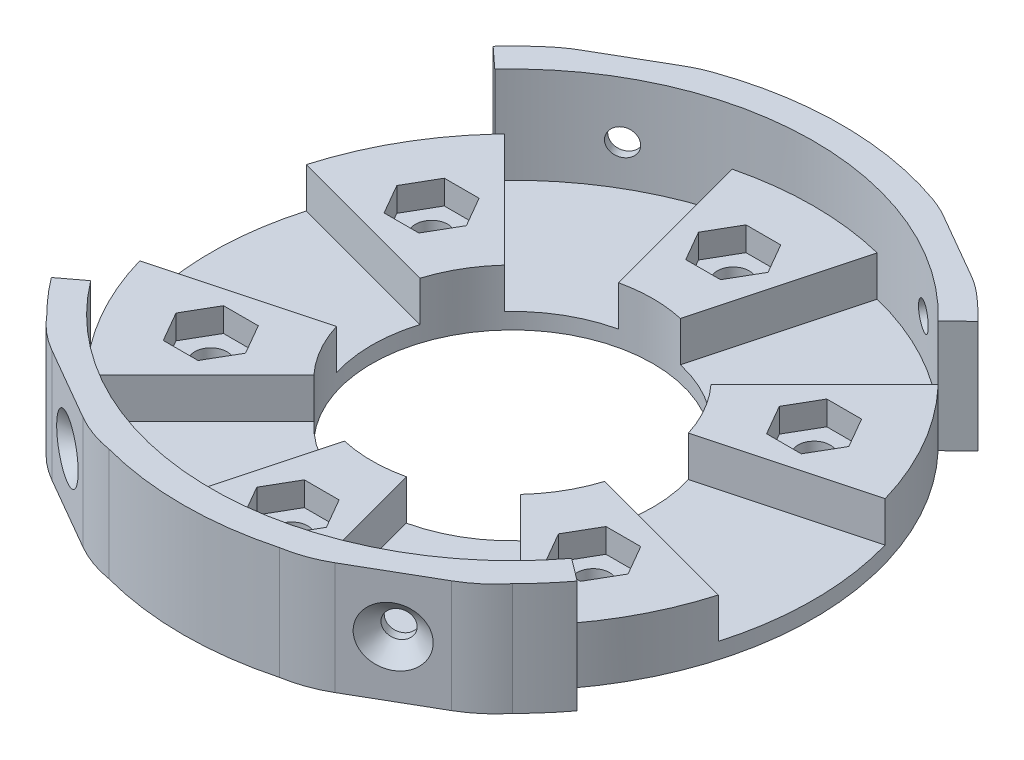
SolidWorks part; units mm, degrees
ref_plane "Front" through (0, 0, 0) normal (0, 0, 1) x (1, 0, 0)
ref_plane "Top" through (0, 0, 0) normal (0, 1, 0) x (1, 0, 0)
ref_plane "Right" through (0, 0, 0) normal (1, 0, 0) x (0, 0, -1)
sketch "Sketch1" plane through (0, 0, 0) normal (0, 1, 0) x (1, 0, 0)
  line L0 (21.6506, 17.5) -> (19.4856, 13.75)
  line L1 (4.3301, 27.5) -> (2.1651, 31.25)
  line L2 (2.1651, 31.25) -> (-2.1651, 31.25)
  line L3 (-2.1651, 31.25) -> (-4.3301, 27.5)
  line L4 (-4.3301, 27.5) -> (-2.1651, 23.75)
  line L5 (-2.1651, 23.75) -> (2.1651, 23.75)
  line L6 (2.1651, 23.75) -> (4.3301, 27.5)
  line L7 (25.9808, 17.5) -> (21.6506, 17.5)
  line L8 (28.1458, 13.75) -> (25.9808, 17.5)
  line L9 (25.9808, 10) -> (28.1458, 13.75)
  line L10 (19.4856, 13.75) -> (21.6506, 10)
  line L11 (21.6506, 10) -> (25.9808, 10)
  line L12 (25.9808, -10) -> (21.6506, -10)
  line L13 (28.1458, -13.75) -> (25.9808, -10)
  line L14 (25.9808, -17.5) -> (28.1458, -13.75)
  line L15 (21.6506, -17.5) -> (25.9808, -17.5)
  line L16 (21.6506, -10) -> (19.4856, -13.75)
  line L17 (19.4856, -13.75) -> (21.6506, -17.5)
  line L18 (4.3301, -27.5) -> (2.1651, -23.75)
  line L19 (2.1651, -31.25) -> (4.3301, -27.5)
  line L20 (-2.1651, -31.25) -> (2.1651, -31.25)
  line L21 (-4.3301, -27.5) -> (-2.1651, -31.25)
  line L22 (2.1651, -23.75) -> (-2.1651, -23.75)
  line L23 (-2.1651, -23.75) -> (-4.3301, -27.5)
  line L24 (-21.6506, -17.5) -> (-19.4856, -13.75)
  line L25 (-25.9808, -17.5) -> (-21.6506, -17.5)
  line L26 (-28.1458, -13.75) -> (-25.9808, -17.5)
  line L27 (-25.9808, -10) -> (-28.1458, -13.75)
  line L28 (-19.4856, -13.75) -> (-21.6506, -10)
  line L29 (-21.6506, -10) -> (-25.9808, -10)
  line L30 (-25.9808, 10) -> (-21.6506, 10)
  line L31 (-28.1458, 13.75) -> (-25.9808, 10)
  line L32 (-25.9808, 17.5) -> (-28.1458, 13.75)
  line L33 (-21.6506, 17.5) -> (-25.9808, 17.5)
  line L34 (-21.6506, 10) -> (-19.4856, 13.75)
  line L35 (-19.4856, 13.75) -> (-21.6506, 17.5)
  line L36 (23.8157, 13.75) -> (15.1554, 8.75)
  line L37 (23.8157, 13.75) -> (32.476, 18.75)
  line L38 (0, 0) -> (9.7057, 36.2222)
  line L39 (0, 0) -> (26.5165, 26.5165)
  line L40 (-9.0279, 36.3971) -> (-3.8496, 17.0713)
  line L41 (26.5165, 26.5165) -> (23.8157, 13.75)
  line L42 (0, 0) -> (36.2222, 9.7057)
  line L43 (0, 0) -> (36.2222, -9.7057)
  line L44 (0, 0) -> (26.5165, -26.5165)
  line L45 (0, 0) -> (9.7057, -36.2222)
  line L46 (0, 0) -> (-9.7057, -36.2222)
  line L47 (0, 0) -> (-26.5165, -26.5165)
  line L48 (0, 0) -> (-36.2222, -9.7057)
  line L49 (0, 0) -> (-36.2222, 9.7057)
  line L50 (0, 0) -> (-26.5165, 26.5165)
  line L51 (0, 0) -> (-9.7057, 36.2222)
  line L52 (0, 0) -> (0, 37.5)
  line L53 (9.0279, 36.3971) -> (3.8496, 17.0713)
  line L54 (27.0069, 26.0169) -> (12.8594, 11.8695)
  line L55 (36.0347, 10.3802) -> (16.709, 5.2019)
  line L56 (36.0347, -10.3802) -> (16.709, -5.2019)
  line L57 (27.0069, -26.0169) -> (12.8594, -11.8695)
  line L58 (9.0279, -36.3971) -> (3.8496, -17.0713)
  line L59 (-9.0279, -36.3971) -> (-3.8496, -17.0713)
  line L60 (-27.0069, -26.0169) -> (-12.8594, -11.8695)
  line L61 (-36.0347, -10.3802) -> (-16.709, -5.2019)
  line L62 (-36.0347, 10.3802) -> (-16.709, 5.2019)
  line L63 (-27.0069, 26.0169) -> (-12.8594, 11.8695)
  circle A0 centre (0, 27.5) radius 2.15
  circle A1 centre (0, 0) radius 37.5
  circle A2 centre (0, 27.5) radius 3.75 construction
  circle A3 centre (23.8157, 13.75) radius 3.75 construction
  circle A4 centre (23.8157, 13.75) radius 2.15
  circle A5 centre (23.8157, -13.75) radius 3.75 construction
  circle A6 centre (23.8157, -13.75) radius 2.15
  circle A7 centre (0, -27.5) radius 3.75 construction
  circle A8 centre (0, -27.5) radius 2.15
  circle A9 centre (-23.8157, -13.75) radius 3.75 construction
  circle A10 centre (-23.8157, -13.75) radius 2.15
  circle A11 centre (-23.8157, 13.75) radius 3.75 construction
  circle A12 centre (-23.8157, 13.75) radius 2.15
  circle A13 centre (0, 0) radius 17.5
  point P60 (0, 0)
  point P75 (0, 0)
  point P101 (0, 0)
  dimension "D1" = 4.3
  dimension "D2" = 75
  dimension "D4" = 7.5
  dimension "D6" = 35
  dimension "D3" = 27.5
  dimension "D7" = 23.8157
  dimension "D8" = 15
  dimension "D10" = 0.7
  dimension "D11" = 0.7
  dimension "D12" = 15
  dimension "D5" = 6
  dimension "D9" = 6
  dimension "D13" = 6
extrude "Boss-Extrude2" add sketch "Sketch1" along normal blind 3 contours A13 L52 L5 L4 L3 L2 A1 L40 | A13 L53 A1 L52 L2 L1 L6 L5 | A13 L63 A1 L62 L35 L34 L30 L31 L32 L33 | A13 L36 L10 L0 L7 L41 L54 | A13 L55 A1 L37 L8 L9 L11 L10 L36 | L37 A1 L54 L41 L7 L8 | A13 L57 A1 L56 L17 L16 L12 L13 L14 L15 | A13 L59 A1 L58 L23 L22 L18 L19 L20 L21 | A13 L61 A1 L60 L29 L28 L24 L25 L26 L27
sketch "Sketch2" plane through (0, 0, 0) normal (0, -1, 0) x (-1, 0, 0)
  line L12 (16.709, 5.2019) -> (36.0347, 10.3802) construction
  line L13 (27.0069, 26.0169) -> (12.8594, 11.8695) construction
  line L14 (3.8496, 17.0713) -> (9.0279, 36.3971) construction
  line L15 (-9.0279, 36.3971) -> (-3.8496, 17.0713) construction
  line L16 (-36.0347, 10.3802) -> (-16.709, 5.2019) construction
  line L17 (-12.8594, 11.8695) -> (-27.0069, 26.0169) construction
  line L18 (-16.709, -5.2019) -> (-36.0347, -10.3802) construction
  line L19 (-27.0069, -26.0169) -> (-12.8594, -11.8695) construction
  line L20 (-3.8496, -17.0713) -> (-9.0279, -36.3971) construction
  line L21 (9.0279, -36.3971) -> (3.8496, -17.0713) construction
  line L22 (12.8594, -11.8695) -> (27.0069, -26.0169) construction
  line L23 (36.0347, -10.3802) -> (16.709, -5.2019) construction
  line L24 (16.709, 5.2019) -> (36.0347, 10.3802)
  line L25 (27.0069, 26.0169) -> (12.8594, 11.8695)
  line L26 (3.8496, 17.0713) -> (9.0279, 36.3971)
  line L27 (-9.0279, 36.3971) -> (-3.8496, 17.0713)
  line L28 (-36.0347, 10.3802) -> (-16.709, 5.2019)
  line L29 (-12.8594, 11.8695) -> (-27.0069, 26.0169)
  line L30 (-16.709, -5.2019) -> (-36.0347, -10.3802)
  line L31 (-27.0069, -26.0169) -> (-12.8594, -11.8695)
  line L32 (-3.8496, -17.0713) -> (-9.0279, -36.3971)
  line L33 (9.0279, -36.3971) -> (3.8496, -17.0713)
  line L34 (12.8594, -11.8695) -> (27.0069, -26.0169)
  line L35 (36.0347, -10.3802) -> (16.709, -5.2019)
  circle A0 centre (0, 0) radius 37.5
  circle A1 centre (0, 0) radius 17.5
  circle A2 centre (0, 27.5) radius 2
  circle A3 centre (23.8157, 13.75) radius 2
  circle A4 centre (23.8157, -13.75) radius 2
  circle A5 centre (0, -27.5) radius 2
  circle A6 centre (-23.8157, -13.75) radius 2
  circle A7 centre (-23.8157, 13.75) radius 2
  arc A8 (16.709, 5.2019) -> (12.8594, 11.8695) centre (0, 0) ccw construction
  arc A9 (36.0347, 10.3802) -> (27.0069, 26.0169) centre (0, 0) ccw construction
  arc A10 (3.8496, 17.0713) -> (-3.8496, 17.0713) centre (0, 0) ccw construction
  arc A11 (9.0279, 36.3971) -> (-9.0279, 36.3971) centre (0, 0) ccw construction
  arc A12 (-12.8594, 11.8695) -> (-16.709, 5.2019) centre (0, 0) ccw construction
  arc A13 (-27.0069, 26.0169) -> (-36.0347, 10.3802) centre (0, 0) ccw construction
  arc A14 (-16.709, -5.2019) -> (-12.8594, -11.8695) centre (0, 0) ccw construction
  arc A15 (-36.0347, -10.3802) -> (-27.0069, -26.0169) centre (0, 0) ccw construction
  arc A16 (-3.8496, -17.0713) -> (3.8496, -17.0713) centre (0, 0) ccw construction
  arc A17 (-9.0279, -36.3971) -> (9.0279, -36.3971) centre (0, 0) ccw construction
  arc A18 (12.8594, -11.8695) -> (16.709, -5.2019) centre (0, 0) ccw construction
  arc A19 (27.0069, -26.0169) -> (36.0347, -10.3802) centre (0, 0) ccw construction
  arc A20 (16.709, 5.2019) -> (12.8594, 11.8695) centre (0, 0) ccw
  arc A21 (36.0347, 10.3802) -> (27.0069, 26.0169) centre (0, 0) ccw
  arc A22 (3.8496, 17.0713) -> (-3.8496, 17.0713) centre (0, 0) ccw
  arc A23 (9.0279, 36.3971) -> (-9.0279, 36.3971) centre (0, 0) ccw
  arc A24 (-12.8594, 11.8695) -> (-16.709, 5.2019) centre (0, 0) ccw
  arc A25 (-27.0069, 26.0169) -> (-36.0347, 10.3802) centre (0, 0) ccw
  arc A26 (-16.709, -5.2019) -> (-12.8594, -11.8695) centre (0, 0) ccw
  arc A27 (-36.0347, -10.3802) -> (-27.0069, -26.0169) centre (0, 0) ccw
  arc A28 (-3.8496, -17.0713) -> (3.8496, -17.0713) centre (0, 0) ccw
  arc A29 (-9.0279, -36.3971) -> (9.0279, -36.3971) centre (0, 0) ccw
  arc A30 (12.8594, -11.8695) -> (16.709, -5.2019) centre (0, 0) ccw
  arc A31 (27.0069, -26.0169) -> (36.0347, -10.3802) centre (0, 0) ccw
  point P18 (0, 0)
  dimension "D1" = 4
  dimension "D4" = 75
  dimension "D5" = 35
  dimension "D2" = 27.5
  dimension "D6" = 23.8157
  dimension "D7" = 13.75
  dimension "D3" = 6
extrude "Boss-Extrude3" add sketch "Sketch2" along normal blind 2
sketch "Sketch3" plane through (0, -2, 0) normal (0, -1, 0) x (-1, 0, 0)
  circle A0 centre (0, 0) radius 37.5
  circle A1 centre (0, 0) radius 17.5
  circle A2 centre (0, 27.5) radius 2
  circle A3 centre (23.8157, 13.75) radius 2
  circle A4 centre (23.8157, -13.75) radius 2
  circle A5 centre (0, -27.5) radius 2
  circle A6 centre (-23.8157, -13.75) radius 2
  circle A7 centre (-23.8157, 13.75) radius 2
  point P19 (0, 0)
  dimension "D1" = 6
extrude "Boss-Extrude4" add sketch "Sketch3" along normal blind 2
sketch "Sketch4" plane through (0, -4, 0) normal (0, -1, 0) x (-1, 0, 0)
  line L0 (0, 0) -> (32.7404, -24.6793)
  line L1 (0, 0) -> (-32.7404, -24.6793)
  line L2 (28.9914, -28.9914) -> (0, 0)
  line L3 (-28.9914, -28.9914) -> (0, 0)
  line L4 (0, 0) -> (-32.7404, 24.6793)
  line L5 (0, 0) -> (32.7404, 24.6793)
  line L6 (0, 0) -> (10.6116, -39.603)
  line L7 (0, 0) -> (-10.6116, -39.603)
  line L8 (28.9914, 28.9914) -> (29.6985, 29.6985)
  line L9 (29.6985, 29.6985) -> (10.8704, 40.5689)
  line L10 (10.6116, -39.603) -> (10.8704, -40.5689)
  line L11 (28.9914, -28.9914) -> (29.6985, -29.6985)
  line L12 (-10.6116, -39.603) -> (-10.8704, -40.5689)
  line L13 (-28.9914, -28.9914) -> (-29.6985, -29.6985)
  line L14 (-29.6985, -29.6985) -> (-10.8704, -40.5689)
  line L15 (10.8704, -40.5689) -> (29.6985, -29.6985)
  line L16 (-27.0069, -26.0169) -> (-12.8594, -11.8695) construction
  line L17 (12.8594, -11.8695) -> (27.0069, -26.0169) construction
  line L18 (-3.8496, -17.0713) -> (-9.0279, -36.3971) construction
  line L19 (9.0279, -36.3971) -> (3.8496, -17.0713) construction
  line L20 (10.6116, 39.603) -> (10.8704, 40.5689)
  line L21 (-10.6116, 39.603) -> (-10.8704, 40.5689)
  line L22 (-10.8704, 40.5689) -> (-29.6985, 29.6985)
  line L23 (-28.9914, 28.9914) -> (-29.6985, 29.6985)
  line L24 (0, 0) -> (30.1685, 27.7644)
  line L25 (0, 0) -> (-29.6899, 28.2756)
  line L26 (27.0069, 26.0169) -> (12.8594, 11.8695) construction
  circle A0 centre (0, 0) radius 37.5
  circle A1 centre (0, 0) radius 41
  point P35 (0, 0)
  dimension "D1" = 82
  dimension "D2" = 75
  dimension "D3" = 5
  dimension "D4" = 5
  dimension "D5" = 1
  dimension "D6" = 1
  dimension "D7" = 1
  dimension "D8" = 1
  dimension "D10" = 1
  dimension "D11" = 1
  dimension "D9" = 2
extrude "Boss-Extrude5" add sketch "Sketch4" against normal blind 14
fillet "Fillet1" radius 15 8 edges at (29.6985, 3, 29.6985) (10.8704, 3, 40.5689) (-29.6985, 3, 29.6985) (-10.8704, 3, 40.5689) (15.1489, 3, -38.0987) (25.42, 3, -32.1687) (-25.42, 3, -32.1687) (-15.1489, 3, -38.0987)
sketch "Sketch6" plane through (20.2844, 0, 35.1337) normal (0.5, 0, 0.866) x (0.866, 0, -0.5)
  line L1 (0, 3) -> (0, 10)
  line L2 (5.3159, 10) -> (-5.3159, 10) construction
  line L4 (0, 3) -> (-5.3159, 3)
  line L5 (0, 3) -> (0, -4)
  line L6 (5.3159, -4) -> (-5.3159, -4) construction
  line L7 (-5.3159, 10) -> (-5.3159, -4) construction
  line L8 (0, 3) -> (5.3159, 3)
  line L9 (5.3159, -4) -> (5.3159, 10) construction
  circle A0 centre (0, 3) radius 1.65
  dimension "D1" = 3.3
extrude "Cut-Extrude1" cut sketch "Sketch6" against normal blind 85 contours L5 A0 L8 | L4 A0 L5 | L8 A0 L1 | L1 A0 L4
sketch "Sketch7" plane through (-20.2844, 0, 35.1337) normal (-0.5, 0, 0.866) x (0.866, 0, 0.5)
  line L1 (0, 3) -> (0, 10)
  line L4 (5.3159, 10) -> (-5.3159, 10) construction
  line L8 (0, 3) -> (0, -4)
  line L9 (5.3159, -4) -> (-5.3159, -4) construction
  line L10 (0, 3) -> (-5.3159, 3)
  line L11 (-5.3159, 10) -> (-5.3159, -4) construction
  line L12 (0, 3) -> (5.3159, 3)
  line L13 (5.3159, -4) -> (5.3159, 10) construction
  line L15 (10.3802, -2) -> (-10.3802, -2) construction
  circle A0 centre (0, 3) radius 1.65
  dimension "D1" = 3.3
  dimension "D2" = 5
extrude "Cut-Extrude2" cut sketch "Sketch7" against normal blind 85 contours L8 A0 L12 | L10 A0 L8 | L1 A0 L10 | L12 A0 L1
chamfer "Chamfer2" distance 2 distance2 2 4 edges at (-18.8555, 3, 35.9587) (21.7134, 3, 34.3087) (18.8555, 3, -35.9587) (-21.7134, 3, -34.3087)
